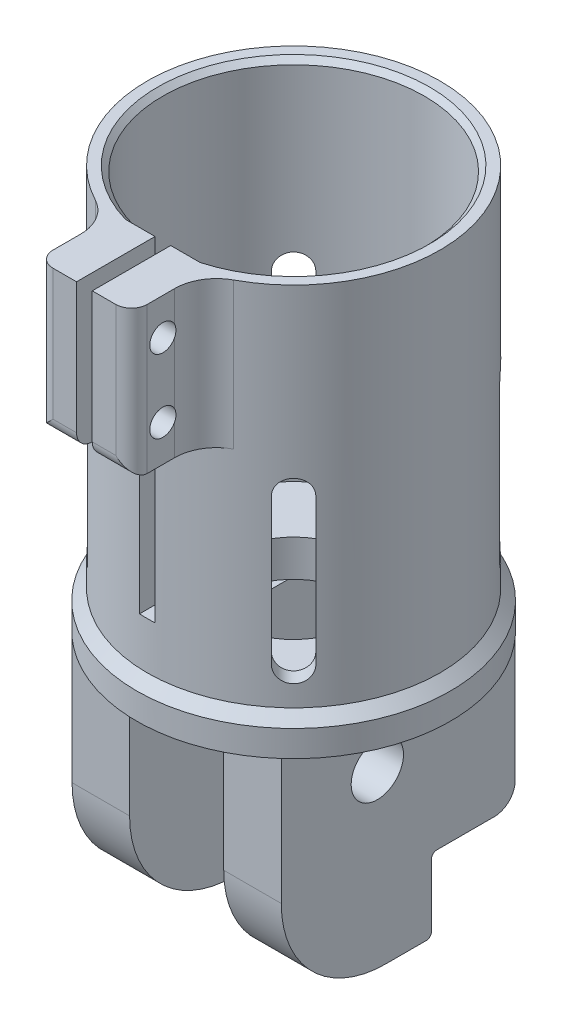
SolidWorks part; units mm, degrees
ref_plane "Front" through (0, 0, 0) normal (0, 0, 1) x (1, 0, 0)
ref_plane "Top" through (0, 0, 0) normal (0, 1, 0) x (1, 0, 0)
ref_plane "Right" through (0, 0, 0) normal (1, 0, 0) x (0, 0, -1)
sketch "Esquisse1" plane through (0, 0, 0) normal (0, 0, 1) x (1, 0, 0)
  line L0 (0, 0) -> (0, 39.8665) construction
  line L1 (-6, 0) -> (-15, 0)
  line L2 (-15, 0) -> (-15, 3.5)
  line L3 (-15, 3.5) -> (-14, 3.5)
  line L4 (-14, 3.5) -> (-14, 38.5)
  line L5 (-14, 38.5) -> (-12.5, 38.5)
  line L6 (-12.5, 38.5) -> (-12.5, 3.5)
  line L7 (-12.5, 3.5) -> (-6, 3.5)
  line L8 (-6, 3.5) -> (-6, 0)
  dimension "D1" = 25
  dimension "D2" = 28
  dimension "D3" = 35
  dimension "D4" = 3.5
  dimension "D5" = 30
  dimension "D6" = 12
revolve "Révolution1" add sketch "Esquisse1" angle 360 about L0
chamfer "Chanfrein1" distance 1 angle 45 1 edges at (0, 3.5, -15)
sketch "Esquisse2" plane through (0, 0, 0) normal (0, -1, 0) x (1, 0, 0)
  line L0 (0, 0) -> (0, 16.0415) construction
  line L1 (-10, 11.1803) -> (-4.5, 11.1803)
  line L2 (-10, 11.1803) -> (-10, -11.1803)
  line L3 (-10, -11.1803) -> (-4.5, -11.1803)
  line L4 (-4.5, 11.1803) -> (-4.5, -11.1803)
  line L5 (4.5, 11.1803) -> (4.5, -11.1803)
  line L6 (10, -11.1803) -> (4.5, -11.1803)
  line L7 (10, 11.1803) -> (10, -11.1803)
  line L8 (10, 11.1803) -> (4.5, 11.1803)
  circle A0 centre (0, 0) radius 15 construction
  dimension "D1" = 20
  dimension "D2" = 9
extrude "Boss.-Extru.1" add sketch "Esquisse2" along normal blind 22
fillet "Congé1" radius 10 2 edges at (-7.25, -22, 11.1803) (7.25, -22, 11.1803)
sketch "Esquisse3" plane through (-10, 0, 0) normal (-1, 0, 0) x (0, 0, 1)
  line L0 (-11.1803, 0) -> (11.1803, 0) construction
  line L1 (-11.1803, -22) -> (-3.1803, -22)
  line L2 (-11.1803, -22) -> (-11.1803, -15)
  line L3 (-11.1803, -15) -> (-3.1803, -15)
  line L4 (-3.1803, -22) -> (-3.1803, -15)
  dimension "D1" = 15
  dimension "D2" = 8
extrude "Enlèv. mat.-Extru.1" cut sketch "Esquisse3" against normal through all
fillet "Congé2" radius 2 2 edges at (7.25, -15, -11.1803) (-7.25, -15, -11.1803)
fillet "Congé3" radius 0.5 4 edges at (7.25, -22, -3.1803) (-7.25, -22, -3.1803) (7.25, -15, -3.1803) (-7.25, -15, -3.1803)
sketch "Esquisse4" plane through (0, 0, 0) normal (1, 0, 0) x (0, 0, -1)
  line L0 (11.1803, 0) -> (-11.1803, 0) construction
  line L1 (-15, 2.5) -> (-15, 0) construction
  circle A0 centre (-2, -5.5) radius 2.5
  dimension "D1" = 5.5
  dimension "D3" = 5
  dimension "D2" = 13
extrude "Enlèv. mat.-Extru.2" cut sketch "Esquisse4" against normal through all both and the other way through all
chamfer "Chanfrein2" distance 0.5 angle 45 1 edges at (0, 38.5, -12.5)
sketch "Esquisse6" plane through (0, 0, 0) normal (1, 0, 0) x (0, 0, -1)
  line L0 (14, 38.5) -> (-14, 38.5) construction
  line L1 (-20, 38.5) -> (-12.5, 38.5)
  line L2 (-20, 38.5) -> (-20, 24.5)
  line L3 (-20, 24.5) -> (-12.5, 24.5)
  line L4 (-12.5, 38.5) -> (-12.5, 24.5)
  dimension "D1" = 12.5
  dimension "D2" = 14
  dimension "D3" = 7.5
extrude "Boss.-Extru.2" add sketch "Esquisse6" along normal mid plane 9
fillet "Congé4" radius 4 2 edges at (4.5, 31.5, 13.2571) (-4.5, 31.5, 13.2571)
fillet "Congé5" radius 1.5 3 edges at (-4.5, 31.5, 20) (0, 24.5, 20) (4.5, 31.5, 20)
sketch "Esquisse5" plane through (0, 0, 0) normal (0, 0, 1) x (1, 0, 0)
  line L0 (14, 38.5) -> (-14, 38.5) construction
  line L1 (-0.75, 69) -> (0.75, 69)
  line L2 (-0.75, 69) -> (-0.75, 8)
  line L3 (-0.75, 8) -> (0.75, 8)
  line L4 (0.75, 69) -> (0.75, 8)
  line L5 (-0.75, 69) -> (0.75, 8) construction
  line L6 (-0.75, 8) -> (0.75, 69) construction
  line L7 (-10, 0) -> (10, 0) construction
  point P0 (0, 38.5)
  dimension "D1" = 8
  dimension "D2" = 1.5
extrude "Enlèv. mat.-Extru.3" cut sketch "Esquisse5" along normal through all
sketch "Esquisse7" plane through (0, 0, 0) normal (1, 0, 0) x (0, 0, -1)
  line L1 (-15.8666, 38.5) -> (-18.5, 38.5) construction
  circle A0 centre (-17, 28) radius 1.25
  circle A1 centre (-17, 35) radius 1.25
  dimension "D1" = 2.5
  dimension "D2" = 7
  dimension "D3" = 3.5
  dimension "D4" = 17
extrude "Enlèv. mat.-Extru.4" cut sketch "Esquisse7" against normal through all both and the other way through all
ref_plane "Plan1" through (9.8995, 0, -9.8995) normal (0.7071, 0, -0.7071) x (0, -1, 0)
sketch "Esquisse8" plane through (9.8995, 0, -9.8995) normal (0.7071, 0, -0.7071) x (0, -1, 0)
  line L0 (-7, 0) -> (-21, 0) construction
  line L1 (-7, -1.5) -> (-21, -1.5)
  line L2 (-7, 1.5) -> (-21, 1.5)
  line L3 (0, 0.8346) -> (0, 14.9768) construction
  arc A0 (-7, -1.5) -> (-7, 1.5) centre (-7, 0) ccw
  arc A1 (-21, 1.5) -> (-21, -1.5) centre (-21, 0) ccw
  point P3 (-14, 0)
  point P8 (-22.5, 0)
  point P9 (-5.5, 0)
  dimension "D1" = 3
  dimension "D2" = 17
  dimension "D3" = 5.5
extrude "Enlèv. mat.-Extru.5" cut sketch "Esquisse8" against normal up to next
pattern_circular "Répétition circulaire1" count 4 over 360 about axis through (0, 0, 0) along (0, -1, 0) of "Enlèv. mat.-Extru.5"
